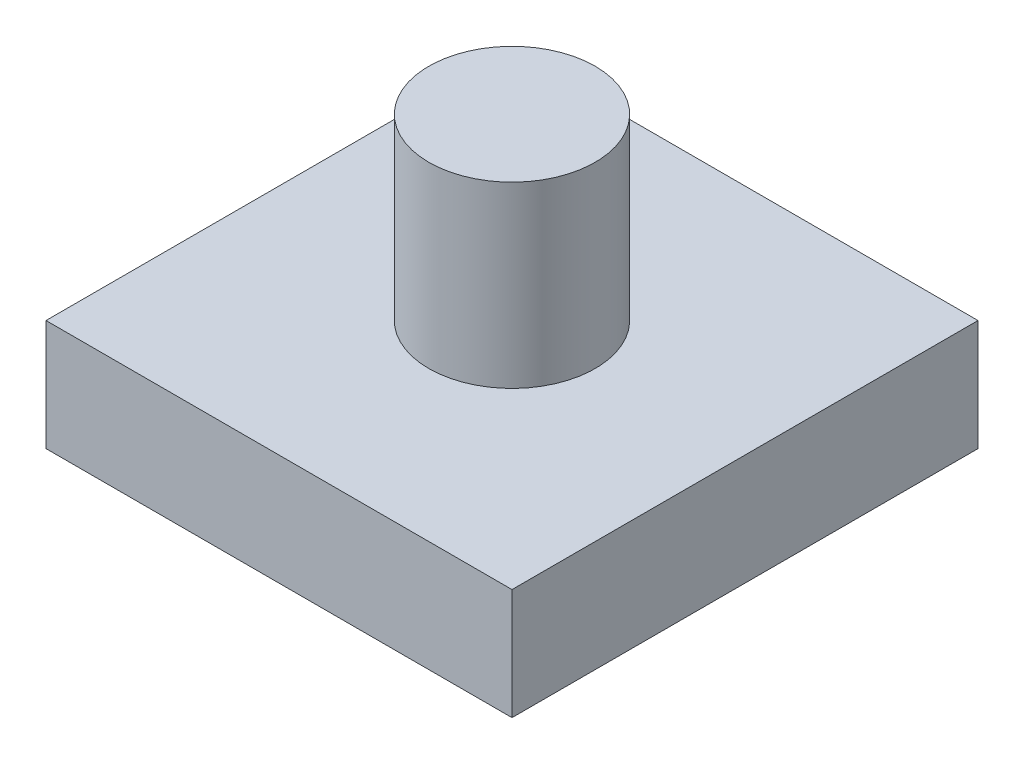
SolidWorks part; units mm, degrees
ref_plane "Front Plane" through (0, 0, 0) normal (0, 0, 1) x (1, 0, 0)
ref_plane "Top Plane" through (0, 0, 0) normal (0, 1, 0) x (1, 0, 0)
ref_plane "Right Plane" through (0, 0, 0) normal (1, 0, 0) x (0, 0, -1)
sketch "Sketch1" plane through (0, 0, 0) normal (0, 1, 0) x (1, 0, 0)
  line L0 (-21, 21) -> (-21, -21)
  line L1 (-21, -21) -> (21, -21)
  line L2 (21, -21) -> (21, 21)
  line L3 (21, 21) -> (-21, 21)
  circle A0 centre (0, 0) radius 7.5
  point P15 (0, 0)
  point P16 (18.4904, 16.0013)
  point P17 (-16.5347, 16.0013)
  point P18 (18.4904, -18.3126)
  dimension "D2" = 21
  dimension "D3" = 21
  dimension "D4" = 15
  dimension "D1" = 42
extrude "Boss-Extrude1" add sketch "Sketch1" along normal blind 10 contours L3 L0 L1 L2
extrude "Boss-Extrude2" add sketch "Sketch1<6>" along normal blind 26.1 contours A0 region at (0, 0, 0)
sketch "Sketch1<6>" plane through (0, 0, 0) normal (0, 1, 0) x (1, 0, 0) same geometry as "Sketch1"
